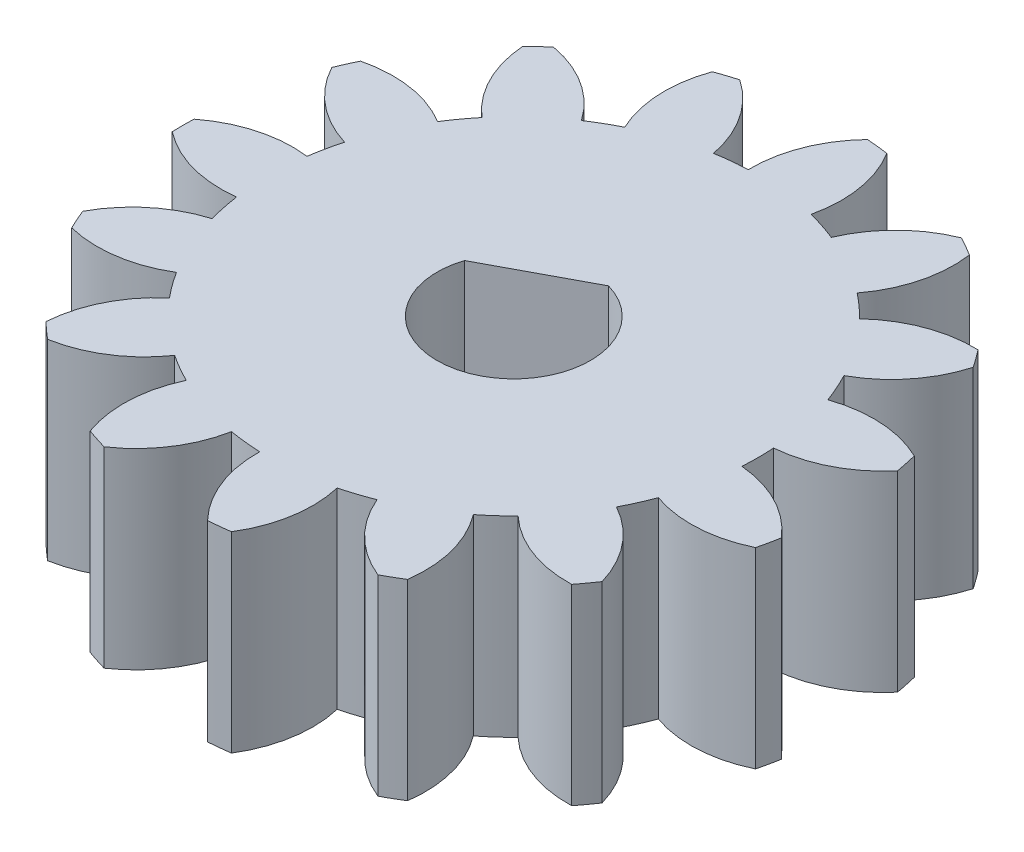
SolidWorks part; units mm, degrees
material "Acrylic (Medium-high impact)"
ref_plane "Front Plane" through (0, 0, 0) normal (0, 0, 1) x (1, 0, 0)
ref_plane "Top Plane" through (0, 0, 0) normal (0, 1, 0) x (1, 0, 0)
ref_plane "Right Plane" through (0, 0, 0) normal (1, 0, 0) x (0, 0, -1)
sketch "Sketch1" plane through (0, 0, 0) normal (0, 1, 0) x (1, 0, 0)
  circle A0 centre (0, 0) radius 56.5317
extrude "Boss-Extrude1" add sketch "Sketch1" along normal blind 5
extrude "Cut-Extrude1" cut sketch "Sketch2" against normal through all contours A74 A73 A72 A71 A70 A18 A19 A20 A21 A13 A12 A11 A10 A25 A24 A23 A22 A29 A28 A27 A26 A33 A32 A31 A30 A37 A36 A35 A34 A41 A40 A39 A38 A45 A44 A43 A42 A49 A48 A47 A46 A53 A52 A51 A50 A57 A56 A55 A54 A61 region at (0, 9.6961, -90.7198)
sketch "Sketch2" plane through (0.054, 9.6961, -2.6905) normal (0, 1, 0) x (0, 0, 1)
  arc A10 (7.0507, 4.4166) -> (7.988, 6.755) centre (4.8627, 6.6506) ccw
  arc A11 (7.988, 6.755) -> (7.5291, 7.0884) centre (2.6905, -0.054) ccw
  arc A12 (7.5291, 7.0884) -> (5.6556, 5.5906) centre (8.3956, 4.0838) ccw
  arc A13 (5.6556, 5.5906) -> (4.7789, 5.9703) centre (2.6905, -0.054) ccw
  arc A18 (3.1034, 6.3087) -> (2.1481, 6.2989) centre (2.6905, -0.054) ccw
  arc A19 (4.2057, 8.4389) -> (3.1034, 6.3087) centre (6.2194, 6.0466) ccw
  arc A20 (4.7605, 8.321) -> (4.2057, 8.4389) centre (2.6905, -0.054) ccw
  arc A21 (4.8554, 5.8036) -> (4.7605, 8.321) centre (1.9479, 6.9545) ccw
  arc A22 (8.4921, 2.2566) -> (10.2994, 4.0116) centre (7.4019, 5.1874) ccw
  arc A23 (10.2994, 4.0116) -> (10.0158, 4.5028) centre (2.6905, -0.054) ccw
  arc A24 (10.0158, 4.5028) -> (7.6951, 3.8966) centre (9.5854, 1.4056) ccw
  arc A25 (7.6951, 3.8966) -> (7.0486, 4.6) centre (2.6905, -0.054) ccw
  arc A26 (8.9303, -0.3029) -> (11.2952, 0.5653) centre (9.1264, 2.818) ccw
  arc A27 (11.2952, 0.5653) -> (11.2359, 1.1294) centre (2.6905, -0.054) ccw
  arc A28 (11.2359, 1.1294) -> (8.8693, 1.5195) centre (9.5829, -1.525) ccw
  arc A29 (8.8693, 1.5195) -> (8.5648, 2.425) centre (2.6905, -0.054) ccw
  arc A30 (8.2896, -2.8193) -> (10.8031, -2.9881) centre (9.7381, -0.0481) ccw
  arc A31 (10.8031, -2.9881) -> (10.9784, -2.4487) centre (2.6905, -0.054) ccw
  arc A32 (10.9784, -2.4487) -> (8.975, -1.1297) centre (8.3887, -4.2012) ccw
  arc A33 (8.975, -1.1297) -> (9.0652, -0.1786) centre (2.6905, -0.054) ccw
  arc A34 (6.6807, -4.8576) -> (8.9083, -6.0342) centre (9.1312, -2.9151) ccw
  arc A35 (8.9083, -6.0342) -> (9.2879, -5.6127) centre (2.6905, -0.054) ccw
  arc A36 (9.2879, -5.6127) -> (7.9942, -3.5929) centre (6.2092, -6.1604) ccw
  arc A37 (7.9942, -3.5929) -> (8.4634, -2.7607) centre (2.6905, -0.054) ccw
  arc A38 (4.3819, -6.0653) -> (5.9384, -8.0462) centre (7.4106, -5.2875) ccw
  arc A39 (5.9384, -8.0462) -> (6.4566, -7.8155) centre (2.6905, -0.054) ccw
  arc A40 (6.4566, -7.8155) -> (6.0962, -5.4441) centre (3.4213, -7.0637) ccw
  arc A41 (6.0962, -5.4441) -> (6.8634, -4.8747) centre (2.6905, -0.054) ccw
  arc A42 (1.7907, -6.2336) -> (2.4068, -8.6763) centre (4.8739, -6.7549) ccw
  arc A43 (2.4068, -8.6763) -> (2.9741, -8.6763) centre (2.6905, -0.054) ccw
  arc A44 (2.9741, -8.6763) -> (3.6094, -6.3634) centre (0.507, -6.7549) ccw
  arc A45 (3.6094, -6.3634) -> (4.5418, -6.1552) centre (2.6905, -0.054) ccw
  arc A46 (-0.645, -5.3334) -> (-1.0757, -7.8155) centre (1.9596, -7.0637) ccw
  arc A47 (-1.0757, -7.8155) -> (-0.5575, -8.0462) centre (2.6905, -0.054) ccw
  arc A48 (-0.5575, -8.0462) -> (0.9637, -6.1917) centre (-2.0297, -5.2875) ccw
  arc A49 (0.9637, -6.1917) -> (1.9001, -6.3808) centre (2.6905, -0.054) ccw
  arc A50 (-2.504, -3.5203) -> (-3.907, -5.6127) centre (-0.8283, -6.1604) ccw
  arc A51 (-3.907, -5.6127) -> (-3.5274, -6.0342) centre (2.6905, -0.054) ccw
  arc A52 (-3.5274, -6.0342) -> (-1.3835, -4.9587) centre (-3.7503, -2.9151) ccw
  arc A53 (-1.3835, -4.9587) -> (-0.6049, -5.5123) centre (2.6905, -0.054) ccw
  arc A54 (-3.4648, -1.1078) -> (-5.5975, -2.4487) centre (-3.0078, -4.2012) ccw
  arc A55 (-5.5975, -2.4487) -> (-5.4222, -2.9881) centre (2.6905, -0.054) ccw
  arc A56 (-5.4222, -2.9881) -> (-3.0262, -2.8776) centre (-4.3572, -0.0481) ccw
  arc A57 (-3.0262, -2.8776) -> (-2.5401, -3.7001) centre (2.6905, -0.054) ccw
  arc A58 (-3.3613, 1.4869) -> (-5.855, 1.1294) centre (-4.202, -1.525) ccw
  arc A59 (-5.855, 1.1294) -> (-5.9143, 0.5653) centre (2.6905, -0.054) ccw
  arc A60 (-5.9143, 0.5653) -> (-3.6805, -0.3083) centre (-3.7455, 2.818) ccw
  arc A61 (-3.6805, -0.3083) -> (-3.5709, -1.2574) centre (2.6905, -0.054) ccw
  arc A62 (-2.2114, 3.8151) -> (-4.6349, 4.5028) centre (-4.2045, 1.4056) ccw
  arc A63 (-4.6349, 4.5028) -> (-4.9185, 4.0116) centre (2.6905, -0.054) ccw
  arc A64 (-4.9185, 4.0116) -> (-3.2331, 2.3049) centre (-2.021, 5.1874) ccw
  arc A65 (-3.2331, 2.3049) -> (-3.5191, 1.3934) centre (2.6905, -0.054) ccw
  arc A66 (-0.2139, 5.4744) -> (-2.1482, 7.0884) centre (-3.0147, 4.0838) ccw
  arc A67 (-2.1482, 7.0884) -> (-2.6071, 6.755) centre (2.6905, -0.054) ccw
  arc A68 (-2.6071, 6.755) -> (-1.7616, 4.5103) centre (0.5182, 6.6506) ccw
  arc A69 (-1.7616, 4.5103) -> (-2.3936, 3.7939) centre (2.6905, -0.054) ccw
  arc A70 (2.2858, 6.1777) -> (1.1752, 8.4389) centre (-0.8385, 6.0466) ccw
  arc A71 (1.1752, 8.4389) -> (0.6204, 8.321) centre (2.6905, -0.054) ccw
  arc A72 (0.6204, 8.321) -> (0.4798, 5.9265) centre (3.433, 6.9545) ccw
  arc A73 (0.4798, 5.9265) -> (-0.389, 5.5291) centre (2.6905, -0.054) ccw
  circle A74 centre (2.6905, -0.054) radius 93.3605
  point P109 (2.6905, -0.054)
sketch "Sketch3" plane through (0, 5, 0) normal (0, 1, 0) x (1, 0, 0)
  line L0 (-1.9022, 0.6178) -> (0.5473, 1.9236)
  arc A0 (-1.9022, 0.6178) -> (0.5473, 1.9236) centre (0, 0) ccw
  dimension "D1" = 4
  dimension "D2" = 1.44
  dimension "D3" = 6.7201
  dimension "D5" = 16.9973
extrude "Cut-Extrude2" cut sketch "Sketch3" against normal through all
